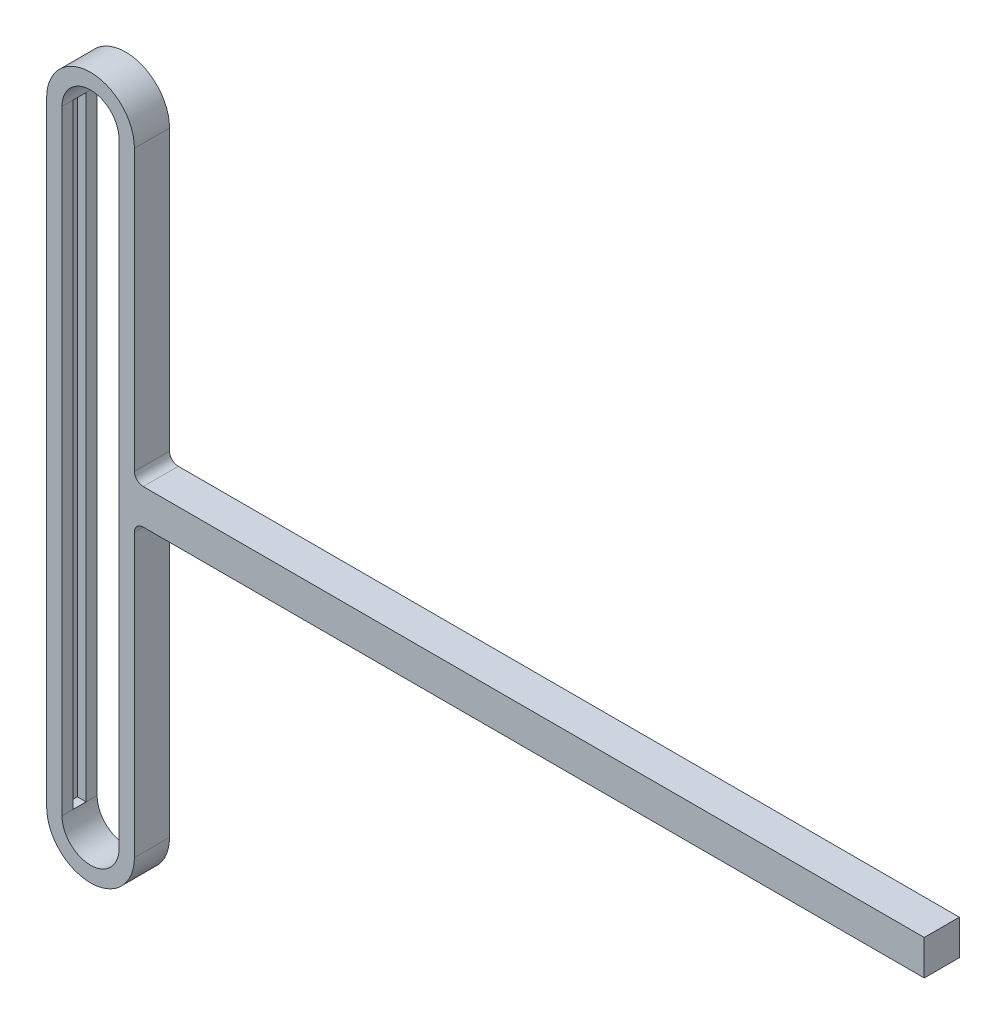
SolidWorks part; units mm, degrees
ref_plane "Front Plane" through (0, 0, 0) normal (0, 0, 1) x (1, 0, 0)
ref_plane "Top Plane" through (0, 0, 0) normal (0, 1, 0) x (1, 0, 0)
ref_plane "Right Plane" through (0, 0, 0) normal (1, 0, 0) x (0, 0, -1)
sketch "Sketch1" plane through (0, 0, 0) normal (0, 0, 1) x (1, 0, 0)
  line L1 (-50, 400) -> (50, 400)
  line L2 (-50, 400) -> (-50, -400)
  line L3 (-50, -400) -> (50, -400)
  line L4 (50, 400) -> (50, -400)
  line L5 (-50, 400) -> (50, -400) construction
  line L6 (-50, -400) -> (50, 400) construction
  point P0 (0, 0)
  dimension "D1" = 800
  dimension "D2" = 100
extrude "Boss-Extrude1" add sketch "Sketch1" along normal blind 40
fillet "Fillet1" 2 edges at (50, 400, 20) (-50, 400, 20) type full round first side face at (50, 0, 20) second side face at (-50, 0, 20) middle face at (0, 400, 20)
fillet "Fillet2" 2 edges at (-50, -400, 20) (50, -400, 20) type full round first side face at (-50, -25, 20) second side face at (50, -25, 20) middle face at (0, -400, 20)
sketch "Sketch2" plane through (0, 0, 0) normal (0, 0, -1) x (-1, 0, 0)
  line L2 (-32.5, 350) -> (-32.5, -350)
  line L4 (32.5, 350) -> (32.5, -350)
  line L5 (-32.5, 350) -> (32.5, -350) construction
  line L6 (-32.5, -350) -> (32.5, 350) construction
  arc A0 (-32.5, 350) -> (32.5, 350) centre (0, 350) cw
  arc A1 (-32.5, -350) -> (32.5, -350) centre (0, -350) ccw
  point P0 (0, 0)
  dimension "D1" = 700
  dimension "D2" = 65
extrude "Cut-Extrude1" cut sketch "Sketch2" against normal through all
sketch "Sketch3" plane through (-32.5, 0, 0) normal (1, 0, 0) x (0, 0, -1)
  line L1 (-27.5, 350) -> (-12.5, 350)
  line L2 (-27.5, 350) -> (-27.5, -350)
  line L3 (-27.5, -350) -> (-12.5, -350)
  line L4 (-12.5, 350) -> (-12.5, -350)
  line L5 (-27.5, 350) -> (-12.5, -350) construction
  line L6 (-27.5, -350) -> (-12.5, 350) construction
  line L7 (0, -350) -> (0, 350) construction
  line L9 (0, -350) -> (0, 350) construction
  point P0 (-20, 0)
  point P9 (0, 0)
  point P10 (0, 0)
  dimension "D1" = 15
  dimension "D2" = 12.5
  dimension "D3" = 700
extrude "Cut-Extrude2" cut sketch "Sketch3" against normal blind 10
mirror "Mirror1" about plane through (0, 0, 0) normal (1, 0, 0) of "Cut-Extrude2"
sketch "Sketch4" plane through (50, 0, 0) normal (1, 0, 0) x (0, 0, -1)
  line L0 (0, -350) -> (0, 350) construction
  line L1 (-40, 21.1798) -> (0, 21.1798)
  line L2 (-40, 21.1798) -> (-40, -18.8202)
  line L3 (-40, -18.8202) -> (0, -18.8202)
  line L4 (0, 21.1798) -> (0, -18.8202)
  line L5 (-40, 21.1798) -> (0, -18.8202) construction
  line L6 (-40, -18.8202) -> (0, 21.1798) construction
  point P0 (-20, 1.1798)
  point P7 (0, 1.1798)
  dimension "D1" = 40
extrude "Boss-Extrude2" add sketch "Sketch4" along normal blind 900
fillet "Fillet3" radius 10 2 edges at (50, -18.8202, 20) (50, 21.1798, 20)
